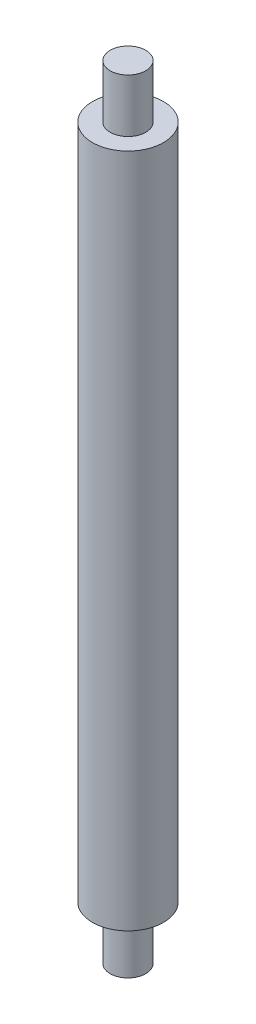
SolidWorks part; units mm, degrees
ref_plane "Plan de face" through (0, 0, 0) normal (0, 0, 1) x (1, 0, 0)
ref_plane "Plan de dessus" through (0, 0, 0) normal (0, 1, 0) x (1, 0, 0)
ref_plane "Plan de droite" through (0, 0, 0) normal (1, 0, 0) x (0, 0, -1)
sketch "Esquisse1" plane through (0, 0, 0) normal (0, 0, 1) x (1, 0, 0)
  line L0 (0, 0) -> (0, 11) construction
  line L1 (0, 11) -> (0.5, 11)
  line L2 (0.5, 11) -> (0.5, 9.5)
  line L3 (0.5, 9.5) -> (1, 9.5)
  line L4 (1, 9.5) -> (1, -9.5)
  line L5 (1, -9.5) -> (0.5, -9.5)
  line L6 (0.5, -9.5) -> (0.5, -11)
  line L7 (0.5, -11) -> (0, -11)
  line L8 (0, 0) -> (1, 0) construction
  line L9 (0, 11) -> (0, -11)
  dimension "D1" = 1
  dimension "D2" = 2
  dimension "D3" = 19
  dimension "D4" = 1.5
revolve "Révolution1" add sketch "Esquisse1" angle 360 about L9
